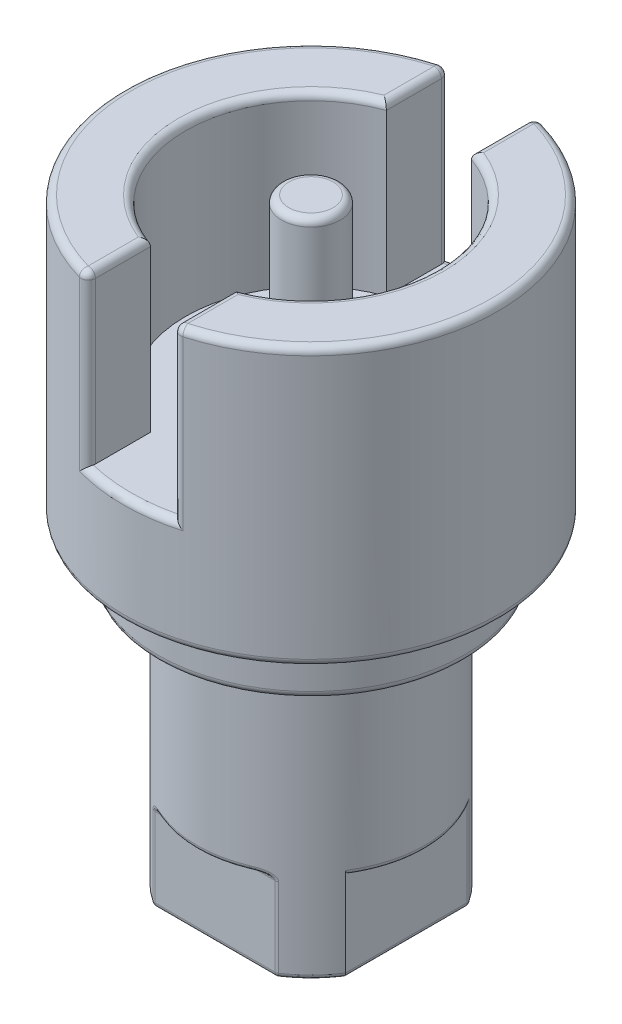
SolidWorks part; units mm, degrees
ref_plane "Piano frontale" through (0, 0, 0) normal (0, 0, 1) x (1, 0, 0)
ref_plane "Piano superiore" through (0, 0, 0) normal (0, 1, 0) x (1, 0, 0)
ref_plane "Piano destro" through (0, 0, 0) normal (1, 0, 0) x (0, 0, -1)
sketch "Schizzo2" plane through (0, 0, 0) normal (1, 0, 0) x (0, 0, -1)
  line L0 (0, 16.6347) -> (0, -15.202) construction
  line L1 (0, 12.5) -> (7.8, 12.5)
  line L2 (7.8, 12.5) -> (7.8, 0.95)
  line L3 (7.8, 0.95) -> (6.4, 0.95)
  line L4 (6.4, 0.95) -> (6.4, -1.2)
  line L5 (6.4, -1.2) -> (4.75, -1.2)
  line L6 (4.75, -1.2) -> (4.75, -12.5)
  line L7 (4.75, -12.5) -> (0, -12.5)
  line L8 (0, 12.5) -> (0, -12.5)
  dimension "D1" = 15.6
  dimension "D2" = 25
  dimension "D3" = 12.8
  dimension "D4" = 9.5
  dimension "D5" = 11.3
  dimension "D6" = 2.15
  dimension "D7" = 11.55
  dimension "D8" = 12.5
revolve "Rivoluzione1" add sketch "Schizzo2" angle 360 about L0
sketch "Schizzo3" plane through (0, 12.5, 0) normal (0, 1, 0) x (1, 0, 0)
  line L0 (0, 8.4401) -> (0, -8.9384) construction
  line L1 (-1.775, 7.5954) -> (-1.775, 4.9143)
  line L2 (1.775, 7.5954) -> (1.775, 4.9143)
  line L3 (-1.775, -4.9143) -> (-1.775, -7.5954)
  line L4 (1.775, -4.9143) -> (1.775, -7.5954)
  circle A0 centre (0, 0) radius 1.225
  arc A1 (-1.775, 4.9143) -> (-1.775, -4.9143) centre (0, 0) ccw
  circle A2 centre (0, 0) radius 7.8 construction
  arc A3 (1.775, 7.5954) -> (-1.775, 7.5954) centre (0, 0) ccw
  arc A4 (1.775, -4.9143) -> (1.775, 4.9143) centre (0, 0) ccw
  arc A5 (-1.775, -7.5954) -> (1.775, -7.5954) centre (0, 0) ccw
  dimension "D1" = 3.55
  dimension "D2" = 10.45
  dimension "D3" = 2.45
extrude "Taglio-Estrusione1" cut sketch "Schizzo3" against normal blind 7
fillet "Raccordo1" radius 1 1 edges at (0, 5.5, 1.225)
fillet "Raccordo2" radius 0.3 17 edges at (-1.775, 9, -7.5954) (-7.8, 12.5, 0) (-1.775, 9, 7.5954) (0, 5.5, 7.8) (1.775, 9, 7.5954) (7.8, 12.5, 0) (1.775, 9, -7.5954) (0, 5.5, -7.8) (0, -1.2, 6.4) (0, 12.5, 1.225) (1.775, 12.5, -6.2548) (1.775, 12.5, 6.2548) (5.225, 12.5, 0) (-1.775, 12.5, -6.2548) (-5.225, 12.5, 0) (-1.775, 12.5, 6.2548) (0, 0.95, 7.8)
sketch "Schizzo4" plane through (0, -12.5, 0) normal (0, -1, 0) x (1, 0, 0)
  line L1 (-4, 4) -> (4, 4)
  line L2 (-4, 4) -> (-4, -4)
  line L3 (-4, -4) -> (4, -4)
  line L4 (4, 4) -> (4, -4)
  line L5 (-4, 4) -> (4, -4) construction
  line L6 (-4, -4) -> (4, 4) construction
  circle A0 centre (0, 0) radius 7.5
  point P0 (0, 0)
  dimension "D2" = 15
  dimension "D1" = 8
extrude "Taglio-Estrusione2" cut sketch "Schizzo4" against normal blind 3.7
hole_wizard "Foro filettato M6-1" positions "Schizzo5" profile "Schizzo6" tap size "M6" standard "ISO"
sketch "Schizzo5" plane through (0, -12.5, 0) normal (0, -1, 0) x (-1, 0, 0)
  point P0 (0, 0)
sketch "Schizzo6" plane through (0, -12.5, 0) normal (1, 0, 0) x (0, 0, -1)
  line L0 (0, 0) -> (0, 14.5022)
  line L1 (0, 14.5022) -> (2.5, 13)
  line L2 (2.5, 13) -> (2.5, 0)
  line L5 (2.5, 0) -> (0, 0)
  line L10 (0, 14.5022) -> (-2.5, 13) construction
  line L11 (0, -6.35) -> (0, 107.95) construction
  dimension "Tap Drill Dia." = 5
  dimension "Tap Drill Depth" = 13
  dimension "Drill Angle" = 118
cosmetic thread "Filettatura del foro1" parameters "D1"=10, "D2"=6
fillet "Raccordo3" radius 0.2 21 edges at (2.5617, -10.65, 4) (0, -8.8, 4) (0, -8.8, 4.75) (0, -1.2, 4.75) (0, -8.8, -4.75) (4.75, -8.8, 0) (-4.75, -8.8, 0) (-2.5617, -10.65, 4) (-4, -10.65, 2.5617) (-4, -10.65, -2.5617) (-2.5617, -10.65, -4) (2.5617, -10.65, -4) (4, -10.65, -2.5617) (3.3588, -12.5, 3.3588) (0, -12.5, 4) (-3.3588, -12.5, 3.3588) (-4, -12.5, 0) (-3.3588, -12.5, -3.3588) (0, -12.5, -4) (3.3588, -12.5, -3.3588) (4, -12.5, 0)
move or copy body "Corpo-Sposta/copia1" [suppressed] bodies to move or copy 105
equation "\"D8@Schizzo2\"=\"D2@Schizzo2\"/2"
